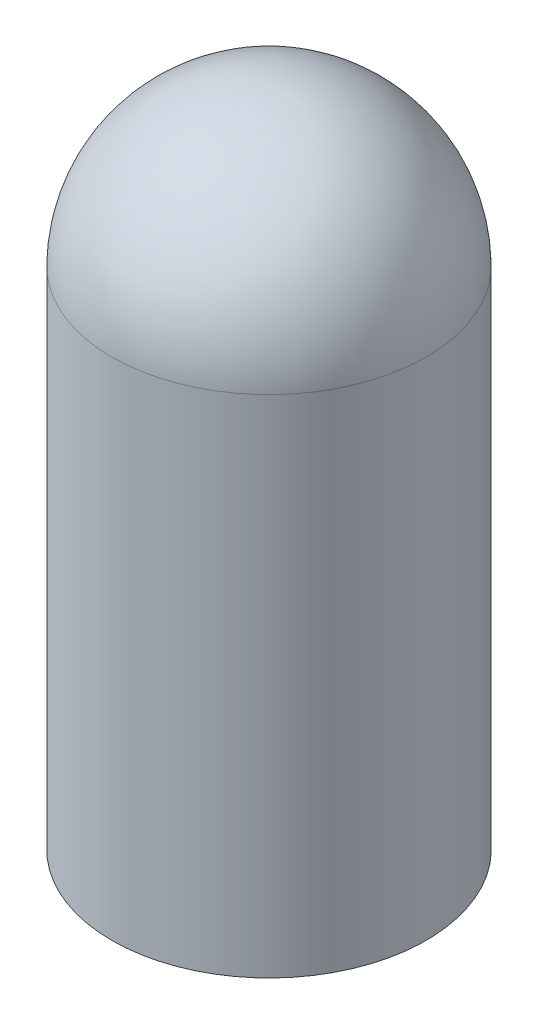
SolidWorks part; units mm, degrees
material "Glass"
ref_plane "Front Plane" through (0, 0, 0) normal (0, 0, 1) x (1, 0, 0)
ref_plane "Top Plane" through (0, 0, 0) normal (0, 1, 0) x (1, 0, 0)
ref_plane "Right Plane" through (0, 0, 0) normal (1, 0, 0) x (0, 0, -1)
sketch "Sketch1" plane through (0, 0, 0) normal (0, 1, 0) x (1, 0, 0)
  circle A0 centre (0, 0) radius 51.3588
  dimension "D1" = 102.7176
extrude "Boss-Extrude1" add sketch "Sketch1" along normal blind 165.1
dome "Dome1" faces to dome 1 distance 50.8 reverse direction no elliptical dome no face at (0, 165.1, 51.3588) parameters "D1"=50.8
shell "Shell1" thickness 0.5588 removed face at (0, 0, 51.3588)
